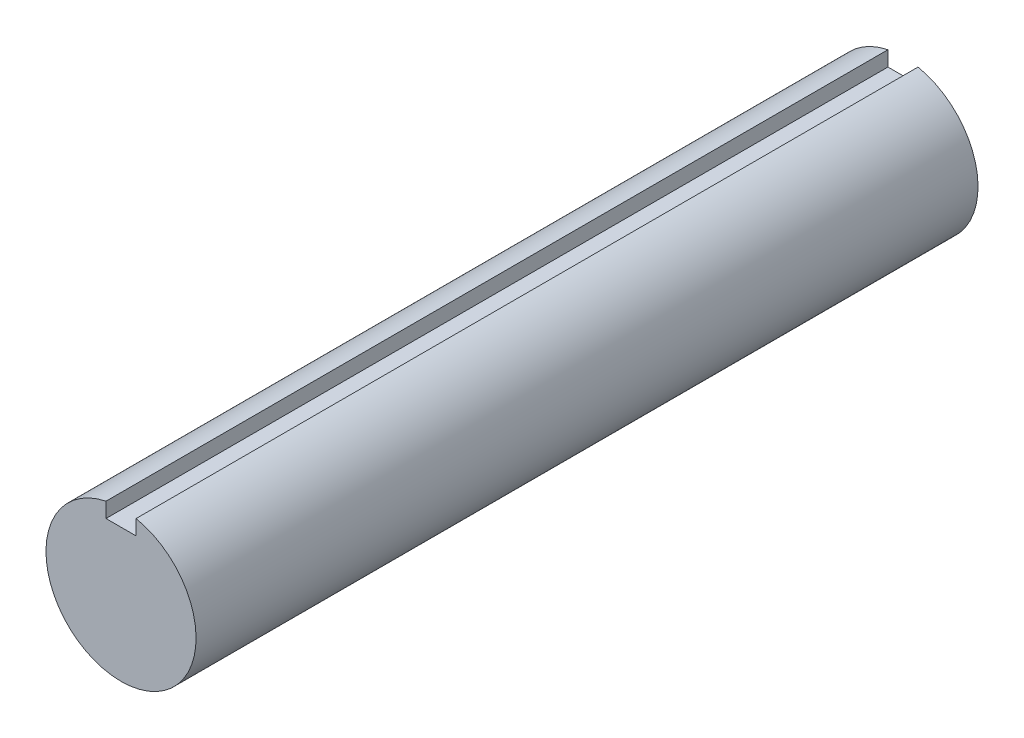
SolidWorks part; units mm, degrees
material "CK45"
ref_plane "Front Plane" through (0, 0, 0) normal (0, 0, 1) x (1, 0, 0)
ref_plane "Top Plane" through (0, 0, 0) normal (0, 1, 0) x (1, 0, 0)
ref_plane "Right Plane" through (0, 0, 0) normal (1, 0, 0) x (0, 0, -1)
sketch "Sketch1" plane through (0, 0, 0) normal (0, 0, 1) x (1, 0, 0)
  circle A0 centre (0, 0) radius 24.95
  dimension "D1" = 49.9
extrude "Boss-Extrude1" add sketch "Sketch1" along normal blind 260
ref_plane "Plane1" through (0, 0, 5) normal (0, 0, -1) x (-1, 0, 0)
sketch "Sketch2" plane through (0, 0, 0) normal (0, 0, -1) x (-1, 0, 0)
  line L1 (-5, 19.45) -> (5, 19.45)
  line L2 (-5, 19.45) -> (-5, 30.8678)
  line L3 (-5, 30.8678) -> (5, 30.8678)
  line L4 (5, 19.45) -> (5, 30.8678)
  line L5 (-5, 19.45) -> (5, 30.8678) construction
  line L6 (-5, 30.8678) -> (5, 19.45) construction
  point P0 (0, 25.1589)
  dimension "D1" = 19.45
  dimension "D2" = 10
extrude "Cut-Extrude1" cut sketch "Sketch2" against normal through all
sketch "Sketch3" plane through (0, 0, 0) normal (0, 0, -1) x (-1, 0, 0)
  circle A0 centre (0, 0) radius 3.5
  dimension "D1" = 7
extrude "Cut-Extrude2" cut sketch "Sketch3" against normal blind 30
thread "Thread1" pitch 1.75 method extrude profile "Thread Profile1" start angle 0, offset 0, length 20, pitch 1.75, diameter 7
ref_plane "Plane2" through (3.5, 0, 0) normal (0, -1, 0) x (1, 0, 0)
sketch "Thread Profile1" plane through (3.5, 0, 0) normal (0, -1, 0) x (1, 0, 0)
  line L0 (0, 0) -> (0, 1.75) construction
  line L11 (0, 0) -> (0, 1.5312)
  line L12 (0, 1.5312) -> (-0.9472, 0.9844)
  line L13 (-0.9472, 0.9844) -> (-0.9472, 0.5469)
  line L15 (-0.9472, 0.5469) -> (0, 0)
  line L17 (-0.9472, 0.7656) -> (0, 0.7656) construction
  point P2 (0, 0)
  dimension "Pitch" = 1.75
  dimension "Profile_Angle" = 60
  dimension "Profile_Land" = 0.4375
  dimension "Profile_Height" = 0.9472
